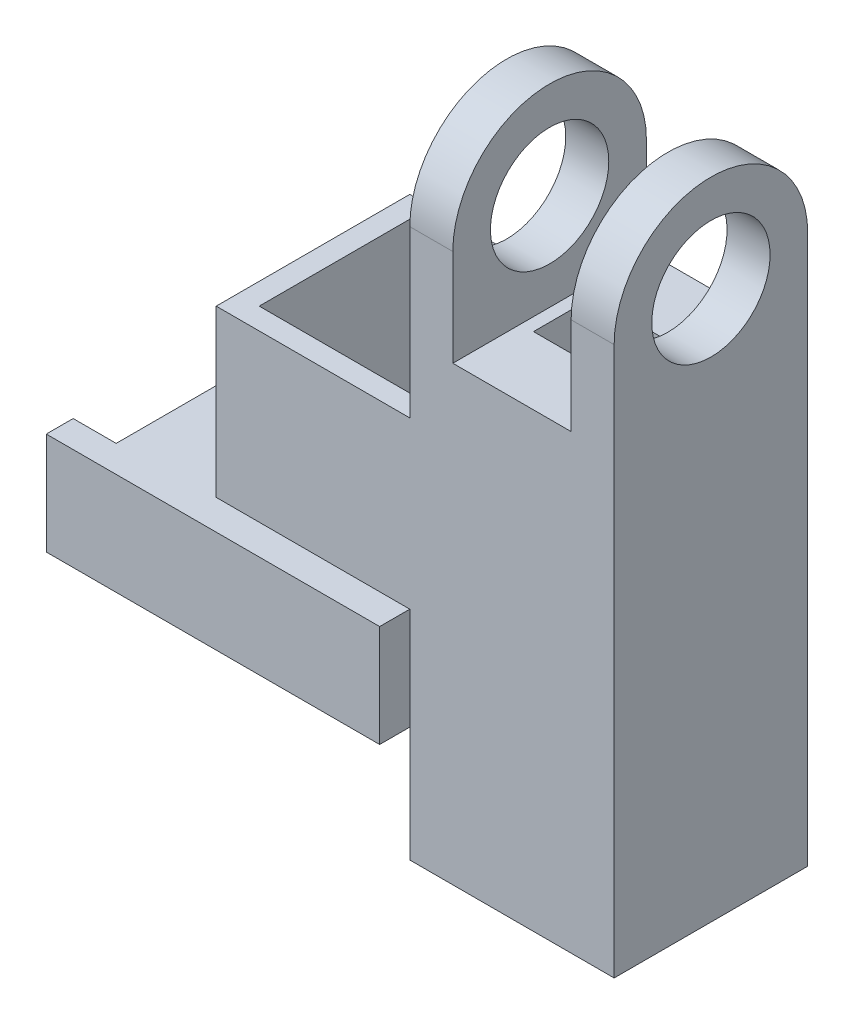
SolidWorks part; units mm, degrees
ref_plane "Front Plane" through (0, 0, 0) normal (0, 0, 1) x (1, 0, 0)
ref_plane "Top Plane" through (0, 0, 0) normal (0, 1, 0) x (1, 0, 0)
ref_plane "Right Plane" through (0, 0, 0) normal (1, 0, 0) x (0, 0, -1)
sketch "Sketch2" plane through (0, 0, 0) normal (1, 0, 0) x (0, 0, -1)
  line L0 (0, 0) -> (18, 0)
  line L1 (18, 0) -> (18, 13)
  line L2 (0, 13) -> (0, 0)
  arc A0 (18, 13) -> (0, 13) centre (9, 13) ccw
  circle A1 centre (9, 13) radius 5.5
  dimension "D3" = 11
  dimension "D1" = 18
  dimension "D4" = 13
extrude "Boss-Extrude1" add sketch "Sketch2" along normal blind 19
sketch "Sketch3" plane through (0, 0, 0) normal (0, 0, 1) x (1, 0, 0)
  line L0 (0, 0) -> (19, 0)
  line L1 (19, 0) -> (19, 22)
  line L2 (19, 22) -> (15, 22)
  line L3 (19, 22) -> (0, 22) construction
  line L4 (15, 22) -> (15, 4)
  line L5 (15, 4) -> (4, 4)
  line L6 (4, 4) -> (4, 22)
  line L7 (4, 22) -> (0, 22)
  line L8 (0, 22) -> (0, 0)
  line L9 (4, 22) -> (15, 22)
  dimension "D1" = 4
  dimension "D2" = 11
  dimension "D3" = 4
extrude "Cut-Extrude1" cut sketch "Sketch3" against normal through all both and the other way through all contours L9 L6 L5 L4 region at (9.5, 13, 0)
sketch "Sketch4" plane through (0, 0, 0) normal (0, 1, 0) x (1, 0, 0)
  line L0 (19, 0) -> (19, 18) construction
  line L1 (5.2, 6.3) -> (13.7, 6.3)
  line L2 (5.2, 6.3) -> (5.2, 11.8)
  line L3 (5.2, 11.8) -> (13.7, 11.8)
  line L4 (13.7, 6.3) -> (13.7, 11.8)
  line L5 (19, 0) -> (0, 0) construction
  dimension "D1" = 8.5
  dimension "D2" = 5.5
  dimension "D3" = 5.3
  dimension "D4" = 6.3
extrude "Cut-Extrude4" cut sketch "Sketch4" along normal blind 19
sketch "Sketch5" plane through (0, 0, 0) normal (0, -1, 0) x (1, 0, 0)
  line L0 (19, 0) -> (0, -18) construction
  line L1 (0, -18) -> (19, -18)
  line L2 (19, -18) -> (0, 0) construction
  line L3 (19, -18) -> (19, 0)
  line L4 (19, 0) -> (0, 0)
  line L5 (0, 0) -> (0, -18)
  circle A0 centre (9.5, -9) radius 8
  dimension "D1" = 16
extrude "Boss-Extrude4" add sketch "Sketch5" along normal blind 20
sketch "Sketch6" plane through (0, 0, 0) normal (-1, 0, 0) x (0, 0, 1)
  line L0 (-9, 13) -> (-9, 4)
  line L1 (-18, 4) -> (0, 4)
  line L2 (0, 13) -> (0, -20) construction
  circle A0 centre (-9, 13) radius 5.5
  arc A1 (0, 13) -> (-18, 13) centre (-9, 13) ccw construction
  point P9 (-9, 4)
  dimension "D2" = 11
  dimension "D3" = 9
  dimension "D1" = 9
  dimension "D4" = 24
sketch3d "3DSketch1"
  line L0 (9.5, -20, -9) -> (9.5, 0, -9) construction
  line L2 (0, -20, 0) -> (0, -20, -18)
  line L3 (0, -20, 0) -> (19, -20, 0)
  line L4 (19, -20, 0) -> (19, -20, -18)
  line L5 (0, -20, -18) -> (19, -20, -18)
  line L6 (0, -20, 0) -> (19, -20, -18) construction
  line L7 (19, -20, 0) -> (0, -20, -18) construction
  circle A0 centre (9.5, -20, -9) radius 8
  point P2 (9.5, -12, -9)
extrude "Boss-Extrude5" add sketch "3DSketch1" along direction (0, 1, 0) on the side against the normal blind 18 contours L3 L2 L5 L4 | A0
sketch "Sketch7" plane through (0, 0, 0) normal (-1, 0, 0) x (0, 0, 1)
  line L0 (0, 13) -> (-18, 13)
  line L1 (-18, 4) -> (-18, -33.8) construction
  line L2 (-18, -38) -> (-18, 13) construction
  line L3 (-18, 4) -> (0, 4) construction
  line L4 (0, 4) -> (0, -33.8) construction
  line L5 (0, 13) -> (0, -38) construction
  line L6 (0, -33.8) -> (-18, -33.8) construction
  line L7 (-7, -33.8) -> (-7, -31.8)
  line L8 (-16, -31.8) -> (-2, -31.8) construction
  line L9 (-16, -31.8) -> (-16, 2) construction
  line L10 (-16, 2) -> (-2, 2) construction
  line L11 (-2, -31.8) -> (-2, 2) construction
  line L12 (-16, -31.8) -> (-2, 2) construction
  line L13 (-16, 2) -> (-2, -31.8) construction
  line L14 (-11, -33.8) -> (-11, -31.8)
  line L15 (-18, -6) -> (-16, -6)
  line L16 (-11, 4) -> (-11, 2)
  line L17 (-7, 4) -> (-7, 2)
  line L18 (0, -6) -> (-2, -6)
  line L19 (0, -23.8) -> (-2, -23.8)
  line L20 (-18, -23.8) -> (-16, -23.8)
  line L21 (-18, 13) -> (-18, -24.8)
  line L22 (-18, 13) -> (0, 13)
  line L23 (0, 13) -> (0, -24.8)
  line L24 (0, -24.8) -> (-18, -24.8)
  line L25 (-7, -24.8) -> (-7, -22.8)
  line L26 (-16, -22.8) -> (-2, -22.8)
  line L27 (-16, -22.8) -> (-16, 11)
  line L28 (-16, 11) -> (-2, 11)
  line L29 (-2, -22.8) -> (-2, 11)
  line L30 (-11, -24.8) -> (-11, -22.8)
  line L31 (-18, 3) -> (-16, 3)
  line L32 (-11, 13) -> (-11, 11)
  line L33 (-7, 13) -> (-7, 11)
  line L34 (0, 3) -> (-2, 3)
  line L35 (0, -14.8) -> (-2, -14.8)
  line L36 (-18, -14.8) -> (-16, -14.8)
  line L37 (-16, -22.8) -> (-2, 11) construction
  line L38 (-16, 11) -> (-2, -22.8) construction
  point P3 (-9, -14.9)
  point P5 (-9, 13)
  point P20 (-18, -23.8)
  point P21 (0, -23.8)
  point P22 (-11, -33.8)
  point P23 (-7, -33.8)
  point P28 (0, -6)
  point P29 (-18, -6)
  point P30 (-11, 4)
  point P31 (-7, 4)
  point P47 (-9, -5.9)
  point P55 (-18, -14.8)
  point P56 (0, -14.8)
  point P57 (-11, -24.8)
  point P58 (-7, -24.8)
  point P63 (0, 3)
  point P64 (-18, 3)
  point P65 (-11, 13)
  line M6 (0, -38) -> (0, 13)
  line M8 (-18, 13) -> (-18, -38)
  dimension "D1" = 18
  dimension "D2" = 37.8
  dimension "D3" = 18
  dimension "D4" = 2
  dimension "D5" = 2
  dimension "D6" = 2
  dimension "D7" = 2
  dimension "D8" = 10
  dimension "D9" = 7
  dimension "D10" = 7
  dimension "D11" = 10
  dimension "D12" = 10
  dimension "D13" = 10
  dimension "D14" = 7
  dimension "D15" = 7
  dimension "D16" = 2
extrude "Boss-Extrude8" add sketch "Sketch7" along normal blind 10 contours L35 L29 L26 L25 L24 M6 | L36 L21 L24 L30 L26 L27 M8 region at (0, -19.3, -0.1221) region at (0, -14.9221, -17)
sketch "Sketch8" plane through (-10, 0, 0) normal (-1, 0, 0) x (0, 0, 1)
  line L0 (-18, -24.8) -> (0, -24.8)
  line L1 (-9, -24.8) -> (-9, -8.709)
  line L2 (-18.3, -24.8) -> (0.3, -24.8)
  line L3 (-18.3, -24.8) -> (-18.3, -17.8)
  line L4 (-18.3, -17.8) -> (0.3, -17.8)
  line L5 (0.3, -24.8) -> (0.3, -17.8)
  line L6 (-18, -17.8) -> (-18, -14.8)
  line L7 (-18, -14.8) -> (-16, -14.8)
  line L8 (-16, -14.8) -> (-16, -17.8)
  line L9 (-16, -22.8) -> (-16, -14.8) construction
  line L10 (-2, -14.8) -> (-2, -17.8)
  line L11 (0, -14.8) -> (-2, -14.8)
  line L12 (0, -17.8) -> (0, -14.8)
  line L13 (-18.3, -17.8) -> (-20.4856, -17.8)
  line L14 (-18.3, -17.8) -> (-20.4856, -17.8)
  line L16 (2.8, -27.3) -> (2.8, -15.3)
  line L17 (-20.8, -27.3) -> (2.8, -27.3)
  line L18 (-20.8, -27.3) -> (-20.8, -15.3)
  line L19 (-18, -27.3) -> (0, -27.3)
  line L20 (-20.8, -15.3) -> (2.8, -15.3) construction
  line L21 (-18.3, -17.8) -> (-20.8, -17.8)
  line L22 (0.3, -17.8) -> (2.8, -17.8)
  circle A0 centre (-14, -21.6) radius 2.1
  circle A1 centre (-4, -21.6) radius 2.1
  point P6 (-14, -21.6)
  point P11 (-4, -21.6)
  point P15 (-9, -24.8)
  point P18 (-9, -17.8)
  line M3 (-16, -14.8) -> (-18, -14.8)
  line M4 (-18, -14.8) -> (-18, -24.8)
  line M5 (-18, -24.8) -> (-11, -24.8)
  line M6 (-11, -24.8) -> (-11, -22.8)
  line M7 (-11, -22.8) -> (-16, -22.8)
  line M8 (-16, -22.8) -> (-16, -14.8)
  dimension "D5" = 4.2
  dimension "D1" = 18.6
  dimension "D2" = 7
  dimension "D3" = 3.8
  dimension "D4" = 4.3
  dimension "D6" = 2.5
extrude "Boss-Extrude19" add sketch "Sketch8" against normal up to surface and the other way blind 14 contours A0 L4 M8 M4 M5 M6 M7 | A0 M8 M7 | A0 L0 L1 L4 M7 M6 M8 | L4 L3 L2 M4 | L2 L5 L4 L1 L0 A1 region at (-10, -21.3, -17.901) region at (-10, -21.3, -18.15) region at (-10, -20.3799, -11.4962) region at (-10, -21.3, -8.8836) region at (-10, -22.6262, -15.9132) up to face at (0, -18.1625, -8.4375)
extrude "Cut-Extrude7" cut sketch "Sketch8<13>" against normal up to surface (10 mm away) contours L20 L6 L4 M8 | L20 L8 M4 M3 | L20 L10 L4 L12 | L10 L20 L12 L11 | A0 | A1 region at (-10, -16.55, -17) region at (-10, -15.05, -17) region at (-10, -16.55, -1) region at (-10, -15.05, -1) up to face at (0, -21.662, -14.738)
sketch "Sketch8<13>" plane through (-10, 0, 0) normal (-1, 0, 0) x (0, 0, 1) same geometry as "Sketch8"
extrude "Boss-Extrude20" add sketch "Sketch8<14>" against normal up to surface and the other way blind 18 contours L22 L5 L2 L0 L3 L13 L21 L18 L17 L16 M5 region at (-10, -25.0544, -14.5) up to face at (0, -21.6, -16.1)
sketch "Sketch8<14>" plane through (-10, 0, 0) normal (-1, 0, 0) x (0, 0, 1) same geometry as "Sketch8"
sketch "Sketch11" plane through (-24, 0, 0) normal (-1, 0, 0) x (0, 0, 1)
  line L0 (-18.3, -24.8) -> (0.3, -24.8)
  line L1 (0.3, -24.8) -> (0.3, -17.8)
  line L2 (0.3, -17.8) -> (-18.3, -17.8)
  line L3 (-18.3, -17.8) -> (-18.3, -24.8)
  circle A0 centre (-14, -21.6) radius 2.1
  circle A1 centre (-4, -21.6) radius 2.1
extrude "Boss-Extrude22" add sketch "Sketch11" along normal blind 3
extrude "Boss-Extrude23" add sketch "Sketch8<15>" along normal blind 21 contours L22 L5 L2 L0 L3 L13 L21 L18 L17 L16 M5 region at (-10, -25.0544, -14.5)
sketch "Sketch8<15>" plane through (-10, 0, 0) normal (-1, 0, 0) x (0, 0, 1) same geometry as "Sketch8"
sketch "Sketch12" plane through (0, 0, 0) normal (-1, 0, 0) x (0, 0, 1)
  line L0 (-18, -17.8) -> (-18, -2.4)
  line L1 (-18, -17.8) -> (-18, 13) construction
  line L2 (-18, -2.4) -> (0, -2.4)
  line L3 (0, 13) -> (0, -17.8) construction
  line L4 (0, -2.4) -> (0, -17.8)
  line L5 (0, -17.8) -> (-18, -17.8)
extrude "Boss-Extrude26" add sketch "Sketch12" along normal blind 18
sketch "Sketch13" plane through (0, -2.4, 0) normal (0, 1, 0) x (1, 0, 0)
  line L0 (-18, 0) -> (-18, 18)
  line L1 (-18, 18) -> (0, 18)
  line L2 (0, 18) -> (0, 0)
  line L3 (0, 0) -> (-18, 0)
  line L4 (-2, 2) -> (-16, 2)
  line L5 (-16, 2) -> (-16, 16)
  line L6 (-16, 16) -> (-2, 16)
  line L7 (-2, 16) -> (-2, 2)
  line L8 (-2, 16) -> (0, 16)
  line L9 (-2, 2) -> (0, 2)
  dimension "D1" = 2
extrude "Cut-Extrude8" cut sketch "Sketch13" against normal up to surface (15.4 mm away) contours L7 L6 L5 L4 | L7 L9 L2 L8 region at (-1, -2.4, -9) region at (-9, -2.4, -9) up to face at (-17.8333, -17.8, -9)
